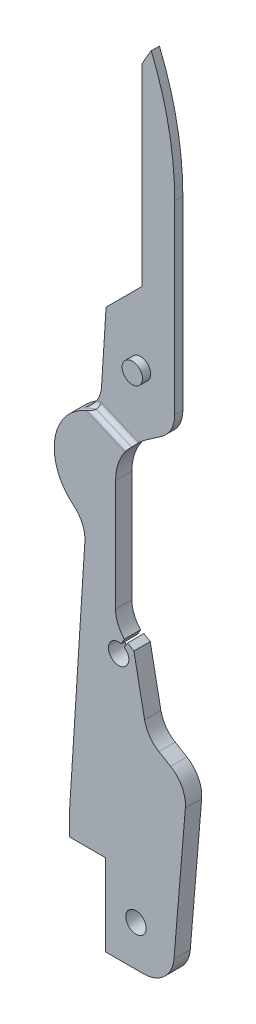
SolidWorks part; units mm, degrees
ref_plane "Płaszczyzna przednia" through (0, 0, 0) normal (0, 0, 1) x (1, 0, 0)
ref_plane "Płaszczyzna górna" through (0, 0, 0) normal (0, 1, 0) x (1, 0, 0)
ref_plane "Płaszczyzna prawa" through (0, 0, 0) normal (1, 0, 0) x (0, 0, -1)
sketch "Sketch1" plane through (0, 0, 0) normal (0, 0, 1) x (1, 0, 0)
  line L0 (0, 67) -> (11.5, 66.2684) construction
  line L1 (0, 0) -> (11.5, 0) construction
  line L2 (0, 0) -> (0, 78) construction
  line L3 (0, 78) -> (11.5, 78) construction
  line L4 (11.5, 0) -> (11.5, 78) construction
  line L5 (0, 47.25) -> (11.5, 46.5184) construction
  line L6 (0, 0) -> (0, 10.4832)
  line L7 (0, 10.4832) -> (1.6002, 35.6375)
  line L8 (9.5, 66.3957) -> (9.5, 46.6457)
  line L9 (9.5, 46.6457) -> (4.5, 43.1446)
  line L10 (4.5, 43.1446) -> (4.5, 27.9946)
  line L11 (4.5, 27.9946) -> (6.3, 26.9554)
  line L12 (6.3, 26.9554) -> (7.6047, 20.3232)
  line L13 (7.6047, 20.3232) -> (11.5, 17.9946)
  line L14 (11.5, 17.9946) -> (10, 0)
  line L15 (10, 0) -> (0, 0)
  line L16 (2.2117, 45.25) -> (3.5809, 66.7722)
  arc A0 (3.5809, 66.7722) -> (7.2002, 78) centre (27.5324, 65.2485) cw
  arc A1 (7.2002, 78) -> (9.5, 66.3957) centre (-20.9268, 66.3957) cw
  arc A2 (2.2117, 45.25) -> (1.6002, 35.6375) centre (3.5809, 40.3372) ccw
  dimension "D8" = 24
  dimension "D9" = 5.1
  dimension "D1" = 78
  dimension "D2" = 11.5
  dimension "D3" = 11
  dimension "D4" = 30.75
  dimension "D5" = 93.64
  dimension "D6" = 86.36
  dimension "D7" = 4
  dimension "D10" = 2
  dimension "D11" = 125
  dimension "D12" = 5
  dimension "D13" = 15.15
  dimension "D14" = 120
  dimension "D15" = 1.8
  dimension "D16" = 132
  dimension "D17" = 10
  dimension "D18" = 10
extrude "Boss-Extrude1" add sketch "Sketch1" along normal mid plane 1.6
fillet "Fillet1" radius 3 1 edges at (10, 0, 0)
sketch "Sketch2" plane through (0, 0, 0.8) normal (0, 0, 1) x (1, 0, 0)
  line L0 (0, 0) -> (7.2397, 0) construction
  line L1 (0, 10.4832) -> (0, 0) construction
  circle A0 centre (6.5, 4) radius 1
  dimension "D1" = 2
  dimension "D3" = 6.5
  dimension "D2" = 4
extrude "Cut-Extrude1" cut sketch "Sketch2" against normal through all
sketch "Sketch3" plane through (0, 0, 0.8) normal (0, 0, 1) x (1, 0, 0)
  line L0 (6.0994, 28.7649) -> (5.0474, 26.9428)
  line L1 (6.0994, 28.7649) -> (6.4025, 28.5899)
  line L3 (6.4025, 28.5899) -> (5.3675, 26.7972)
  line L4 (6.3, 26.9554) -> (4.5, 27.9946) construction
  arc A0 (5.0474, 26.9428) -> (5.3675, 26.7972) centre (4.8, 25.9739) ccw
  dimension "D1" = 2
  dimension "D3" = 1.6
  dimension "D4" = 1.5
  dimension "D2" = 0.35
  dimension "D5" = 1
extrude "Cut-Extrude2" cut sketch "Sketch3" against normal through all
sketch "Sketch4" plane through (0, 0, 0.8) normal (0, 0, 1) x (1, 0, 0)
  line L0 (3.5809, 66.7722) -> (2.2117, 45.25) construction
  line L1 (3.5809, 66.7722) -> (2.2117, 45.25)
  line L2 (6.2683, 76.3768) -> (6.2683, 57.5)
  line L3 (6.2683, 57.5) -> (2.7683, 54)
  arc A0 (7.2002, 78) -> (3.5809, 66.7722) centre (27.5324, 65.2485) ccw construction
  arc A1 (7.2002, 78) -> (3.5809, 66.7722) centre (27.5324, 65.2485) ccw
  dimension "D1" = 24
  dimension "D2" = 3.5
  dimension "D3" = 45
extrude "Cut-Extrude-Thin1" cut sketch "Sketch4" against normal through all thin thin type one direction wall 10
sketch "Sketch5" plane through (0, 0, 0.8) normal (0, 0, 1) x (1, 0, 0)
  line L0 (2.2117, 45.25) -> (15.1142, 39.7732)
  line L1 (15.1142, 39.7732) -> (15.1142, 88.8702)
  line L2 (2.2117, 45.25) -> (2.2117, 88.8702)
  line L3 (2.2117, 88.8702) -> (15.1142, 88.8702)
  dimension "D1" = 113
extrude "Cut-Extrude3" cut sketch "Sketch5" against normal blind 0.8
fillet "Fillet2" radius 3 6 edges at (11.5, 17.9946, 0) (7.6047, 20.3232, 0) (4.5, 27.9946, 0) (1.6002, 35.6375, 0) (2.2117, 45.25, -0.4) (9.5, 46.6457, -0.4)
fillet "Fillet3" radius 5 1 edges at (4.5, 43.1446, 0)
fillet "Fillet4" radius 0.4 3 edges at (1.5386, 45.0104, 0) (3.949, 44.5126, 0.8) (3.949, 44.5126, 0)
sketch "Sketch6" plane through (0, 0, 0) normal (0, 0, 1) x (1, 0, 0)
  line L0 (0, 0) -> (7.2397, 0) construction
  circle A0 centre (6.14, 50.5) radius 1
  dimension "D1" = 2
  dimension "D2" = 6.14
  dimension "D3" = 50.5
extrude "Boss-Extrude2" add sketch "Sketch6" along normal blind 0.8
sketch "Sketch7" plane through (0, 0, 0.8) normal (0, 0, 1) x (1, 0, 0)
  line L1 (0, 0) -> (3.5, 0)
  line L2 (0, 0) -> (0, 8)
  line L3 (0, 8) -> (3.5, 8)
  line L4 (3.5, 0) -> (3.5, 8)
  dimension "D1" = 8
  dimension "D2" = 3.5
extrude "Cut-Extrude4" cut sketch "Sketch7" against normal through all
